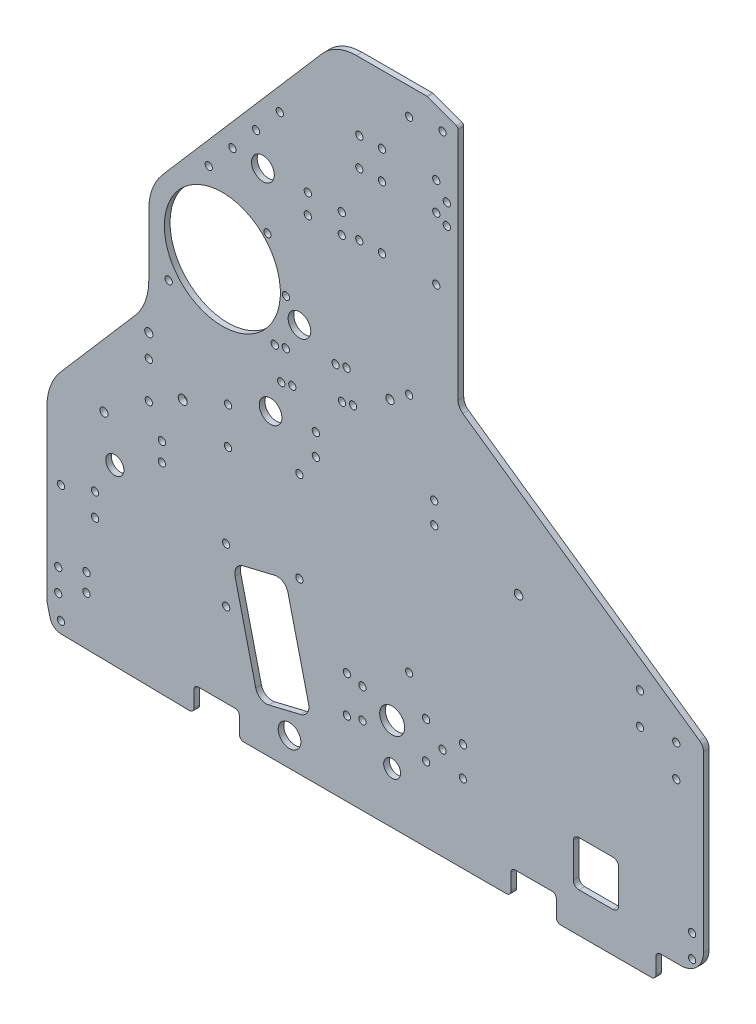
SolidWorks part; units mm, degrees
ref_plane "Front Plane" through (0, 0, 0) normal (0, 0, 1) x (1, 0, 0)
ref_plane "Top Plane" through (0, 0, 0) normal (0, 1, 0) x (1, 0, 0)
ref_plane "Right Plane" through (0, 0, 0) normal (1, 0, 0) x (0, 0, -1)
sketch "Sketch1" plane through (0, 0, 0) normal (0, 0, 1) x (1, 0, 0)
  line L0 (82.55, -20.32) -> (82.55, -6.35)
  line L2 (0, 0) -> (0, 157.48)
  line L4 (368.3, -20.32) -> (368.3, 106.68)
  line L5 (82.55, -6.35) -> (107.95, -6.35)
  line L6 (107.95, -6.35) -> (107.95, -20.32)
  line L7 (107.95, -20.32) -> (260.35, -20.32)
  line L8 (260.35, -20.32) -> (260.35, -6.35)
  line L9 (260.35, -6.35) -> (285.75, -6.35)
  line L10 (285.75, -6.35) -> (285.75, -20.32)
  line L11 (285.75, -20.32) -> (368.3, -20.32)
  line L12 (361.95, 12.7) -> (368.3, 12.7) construction
  line L13 (0, 0) -> (6.35, 0) construction
  line L14 (0.1896, -7.8901) -> (1.7771, -14.2401)
  line L15 (7.8295, -19.0491) -> (82.55, -20.32)
  line L16 (0, 0) -> (0, -6.35)
  line L17 (76.2, 128.905) -> (79.375, 128.905) construction
  line L18 (57.15, 118.5863) -> (101.6, 118.5862) construction
  line L19 (57.15, 118.5863) -> (57.15, 139.2238) construction
  line L20 (101.6, 118.5862) -> (101.6, 139.2237) construction
  line L21 (57.15, 139.2238) -> (101.6, 139.2237) construction
  line L22 (57.15, 118.5863) -> (101.6, 139.2237) construction
  line L23 (101.6, 118.5862) -> (57.15, 139.2238) construction
  line L24 (101.6, 139.2237) -> (125.4682, 147.9111) construction
  line L25 (203.2, 59.805) -> (203.2, 194.805) construction
  line L26 (203.2, 194.805) -> (203.2, 329.805) construction
  line L27 (355.6, 332.105) -> (330.2, 332.105) construction
  line L28 (330.2, 332.105) -> (330.2, 217.805) construction
  line L29 (330.2, 217.805) -> (355.6, 217.805) construction
  line L30 (355.6, 217.805) -> (355.6, 332.105) construction
  line L31 (203.2, 344.805) -> (203.2, 194.805) construction
  line L32 (50.8, 332.105) -> (76.2, 332.105) construction
  line L33 (76.2, 332.105) -> (76.2, 217.805) construction
  line L34 (50.8, 217.805) -> (50.8, 332.105) construction
  line L35 (76.2, 217.805) -> (50.8, 217.805) construction
  line L36 (213.2, 344.805) -> (230.6638, 338.455)
  line L37 (203.2, 344.805) -> (161.925, 344.805)
  line L38 (203.2, 344.805) -> (213.2, 344.805)
  line L39 (348.5362, 344.805) -> (413.4623, 344.805)
  line L40 (348.5362, 344.805) -> (230.6638, 344.805) construction
  line L42 (161.925, 344.805) -> (0, 157.48)
  line L44 (230.6638, 338.455) -> (230.6638, 202.565)
  line L45 (230.6638, 202.565) -> (368.3, 106.68)
  line L46 (213.2, 344.805) -> (-141.0713, 344.805) construction
  circle A0 centre (6.35, 0) radius 2.032
  circle A1 centre (6.35, 12.7) radius 2.032
  circle A2 centre (361.95, 0) radius 2.032
  circle A3 centre (361.95, 12.7) radius 2.032
  arc A5 (1.7771, -14.2401) -> (7.8295, -19.0491) centre (7.9375, -12.7) ccw
  circle A6 centre (7.9375, -12.7) radius 2.032
  arc A7 (0, -6.35) -> (0.1896, -7.8901) centre (6.35, -6.35) ccw
  circle A8 centre (38.1, 78.105) radius 5.08
  circle A9 centre (76.2, 128.905) radius 2.54
  circle A10 centre (101.6, 118.5862) radius 2.032
  circle A11 centre (101.6, 139.2237) radius 2.032
  circle A12 centre (57.15, 139.2238) radius 2.032
  circle A13 centre (57.15, 118.5863) radius 2.032
  circle A15 centre (203.2, 59.805) radius 2
  circle A16 centre (203.2, 194.805) radius 2
  circle A17 centre (203.2, 329.805) radius 2
  circle A18 centre (63.5, 313.055) radius 2.032
  circle A20 centre (355.6, 332.105) radius 2.032
  circle A21 centre (330.2, 332.105) radius 2.032
  circle A22 centre (355.6, 217.805) radius 2.032
  circle A23 centre (330.2, 217.805) radius 2.032
  circle A24 centre (50.8, 332.105) radius 2.032
  circle A25 centre (76.2, 332.105) radius 2.032
  circle A26 centre (50.8, 217.805) radius 2.032
  circle A27 centre (76.2, 217.805) radius 2.032
  circle A28 centre (221.9319, 332.105) radius 2
  circle A29 centre (224.3138, 298.831) radius 2.032
  circle A30 centre (353.06, 100.7351) radius 2.032
  circle A31 centre (332.74, 115.9751) radius 2.032
  circle A32 centre (332.74, 98.1951) radius 2.032
  circle A33 centre (353.06, 82.9551) radius 2.032
  circle A34 centre (117.3562, 280.4276) radius 2.032
  circle A35 centre (104.0678, 265.0548) radius 2.032
  circle A36 centre (90.7795, 249.682) radius 2.032
  circle A38 centre (130.6445, 295.8004) radius 2.032
  circle A39 centre (68.326, 182.9237) radius 2.032
  circle A40 centre (224.3138, 287.401) radius 2.032
  circle A41 centre (125.4682, 147.9111) radius 6.35
  point P82 (203.2, 344.805)
  point P83 (221.9319, 341.63)
  point P90 (368.3, 62.484)
  dimension "D6" = 4.064
  dimension "D10" = 6.35
  dimension "D11" = 4.064
  dimension "D17" = 38.1
  dimension "D27" = 4
  dimension "D31" = 4.064
  dimension "D32" = 41.275
  dimension "D36" = 4.064
  dimension "D47" = 39.624
  dimension "D48" = 4.064
  dimension "D25" = 5.08
  dimension "D26" = 4.064
  dimension "D52" = 4.064
  dimension "D65" = 4.064
  dimension "D69" = 10.16
  dimension "D72" = 12.7
  dimension "D2" = 127
  dimension "D3" = 13.97
  dimension "D4" = 25.4
  dimension "D5" = 152.4
  dimension "D7" = 12.7
  dimension "D8" = 6.35
  dimension "D9" = 20.32
  dimension "D12" = 12.7
  dimension "D13" = 1.5875
  dimension "D14" = 82.55
  dimension "D15" = 368.3
  dimension "D16" = 6.35
  dimension "D18" = 98.425
  dimension "D19" = 38.1
  dimension "D20" = 50.8
  dimension "D21" = 3.175
  dimension "D22" = 270
  dimension "D23" = 20.6375
  dimension "D24" = 44.45
  dimension "D28" = 135
  dimension "D29" = 12.7
  dimension "D30" = 15
  dimension "D33" = 63.5
  dimension "D34" = 27.4638
  dimension "D35" = 12.7
  dimension "D37" = 114.3
  dimension "D38" = 25.4
  dimension "D39" = 12.7
  dimension "D40" = 157.48
  dimension "D41" = 142.24
  dimension "D42" = 365.125
  dimension "D43" = 10
  dimension "D44" = 6.35
  dimension "D45" = 31.75
  dimension "D46" = 6.35
  dimension "D49" = 6.35
  dimension "D50" = 203.2
  dimension "D51" = 15.24
  dimension "D53" = 17.78
  dimension "D54" = 17.78
  dimension "D55" = 20.32
  dimension "D56" = 15.24
  dimension "D57" = 92.202
  dimension "D58" = 8.382
  dimension "D59" = 20.32
  dimension "D60" = 20.32
  dimension "D61" = 8.382
  dimension "D62" = 20.32
  dimension "D63" = 8.382
  dimension "D64" = 8.382
  dimension "D66" = 35.052
  dimension "D67" = 68.326
  dimension "D68" = 11.43
  dimension "D70" = 25.4
  dimension "D71" = 110
extrude "Boss-Extrude1" add sketch "Sketch1" along normal blind 3.175 contours L16 A7 L14 A5 L15 L2 A0 A1 A6 region at (171.5112, 119.5259, 0)
fillet "Fillet1" radius 2.286 4 edges at (285.75, -6.35, 1.5875) (107.95, -6.35, 1.5875) (260.35, -6.35, 1.5875) (82.55, -6.35, 1.5875)
fillet "Fillet2" radius 6.35 1 edges at (230.6638, 202.565, 1.5875)
sketch "Sketch2" plane through (0, 0, 0) normal (0, 0, -1) x (-1, 0, 0)
  circle A0 centre (-100.5528, 71.086) radius 2.032 construction
  circle A1 centre (-100.5528, 40.606) radius 2.032 construction
  circle A2 centre (-22.225, 18.2025) radius 2.032 construction
  circle A3 centre (-22.225, 8.0425) radius 2.032 construction
  circle A4 centre (-100.5528, 71.086) radius 2.032
  circle A5 centre (-100.5528, 40.606) radius 2.032
  circle A6 centre (-22.225, 18.2025) radius 2.032
  circle A7 centre (-22.225, 8.0425) radius 2.032
extrude "Cut-Extrude1" cut sketch "Sketch2" against normal through all
fillet "Fillet3" radius 1.5875 2 edges at (230.6638, 338.455, 1.5875) (213.2, 344.805, 1.5875)
sketch "Sketch3" plane through (0, 0, 3.175) normal (0, 0, 1) x (1, 0, 0)
  line L0 (132.9524, 63.2646) -> (132.7215, 64.2281) construction
  line L1 (128.3814, 66.8897) -> (110.6828, 62.6472) construction
  line L2 (114.5132, 58.4237) -> (126.8822, 61.3887) construction
  line L3 (108.0212, 58.3071) -> (108.2522, 57.3436) construction
  line L4 (131.2006, 57.703) -> (140.0164, 20.9265) construction
  line L5 (144.0993, 16.7636) -> (132.9524, 63.2646) construction
  line L6 (108.2522, 57.3436) -> (119.3991, 10.8426) construction
  line L7 (121.1509, 16.4042) -> (112.3351, 53.1807) construction
  line L8 (119.3991, 10.8426) -> (119.6301, 9.8791) construction
  line L9 (144.3303, 15.8001) -> (144.0993, 16.7636) construction
  line L10 (137.8383, 15.6835) -> (125.4694, 12.7185) construction
  line L11 (123.9701, 7.2175) -> (141.6687, 11.4601) construction
  line L12 (132.9524, 63.2646) -> (132.7215, 64.2281)
  line L13 (128.3814, 66.8897) -> (110.6828, 62.6472)
  line L14 (114.5132, 58.4237) -> (126.8822, 61.3887)
  line L15 (108.0212, 58.3071) -> (108.2522, 57.3436)
  line L16 (131.2006, 57.703) -> (140.0164, 20.9265)
  line L17 (144.0993, 16.7636) -> (132.9524, 63.2646)
  line L18 (108.2522, 57.3436) -> (119.3991, 10.8426)
  line L19 (121.1509, 16.4042) -> (112.3351, 53.1807)
  line L20 (119.3991, 10.8426) -> (119.6301, 9.8791)
  line L21 (144.3303, 15.8001) -> (144.0993, 16.7636)
  line L22 (137.8383, 15.6835) -> (125.4694, 12.7185)
  line L23 (123.9701, 7.2175) -> (141.6687, 11.4601)
  line L24 (127.7894, 69.3598) -> (110.0908, 65.1172)
  line L25 (105.5512, 57.715) -> (105.7822, 56.7515)
  line L26 (105.7822, 56.7515) -> (116.9291, 10.2505)
  line L27 (116.9291, 10.2505) -> (117.16, 9.287)
  line L28 (124.5622, 4.7475) -> (142.2608, 8.99)
  line L29 (146.8003, 16.3922) -> (146.5694, 17.3557)
  line L30 (146.5694, 17.3557) -> (135.4225, 63.8567)
  line L31 (135.4225, 63.8567) -> (135.1915, 64.8202)
  line L32 (14.605, -0.1369) -> (103.7278, 32.3011) construction
  line L33 (14.605, -0.1369) -> (103.7278, 32.3011)
  line L34 (0, -6.35) -> (0, 157.48) construction
  line L35 (-39.6666, 74.7152) -> (103.7278, 126.9065) construction
  line L36 (26.9875, 46.9531) -> (26.9875, 59.6531) construction
  line L37 (107.95, -20.32) -> (260.35, -20.32) construction
  line L38 (64.5259, 92.5258) -> (64.5259, 102.9405) construction
  line L39 (131.6538, 14.201) -> (136.0946, -4.3242) construction
  arc A0 (132.7215, 64.2281) -> (128.6308, 66.9403) centre (129.2206, 63.3889) ccw construction
  arc A1 (110.6828, 62.6472) -> (110.4377, 62.5791) centre (111.522, 59.1463) ccw construction
  arc A2 (128.6308, 66.9403) -> (128.3814, 66.8897) centre (129.2206, 63.3889) ccw construction
  arc A3 (110.4377, 62.5791) -> (108.0212, 58.3071) centre (111.522, 59.1463) ccw construction
  arc A4 (119.6301, 9.8791) -> (123.7207, 7.1669) centre (123.1309, 10.7183) ccw construction
  arc A5 (141.9139, 11.5281) -> (144.3303, 15.8001) centre (140.8295, 14.9609) ccw construction
  arc A6 (141.6687, 11.4601) -> (141.9139, 11.5281) centre (140.8295, 14.9609) ccw construction
  arc A7 (123.7207, 7.1669) -> (123.9701, 7.2175) centre (123.1309, 10.7183) ccw construction
  arc A8 (132.7215, 64.2281) -> (128.6308, 66.9403) centre (129.2206, 63.3889) ccw
  arc A9 (110.6828, 62.6472) -> (110.4377, 62.5791) centre (111.522, 59.1463) ccw
  arc A10 (128.6308, 66.9403) -> (128.3814, 66.8897) centre (129.2206, 63.3889) ccw
  arc A11 (110.4377, 62.5791) -> (108.0212, 58.3071) centre (111.522, 59.1463) ccw
  arc A12 (119.6301, 9.8791) -> (123.7207, 7.1669) centre (123.1309, 10.7183) ccw
  arc A13 (141.9139, 11.5281) -> (144.3303, 15.8001) centre (140.8295, 14.9609) ccw
  arc A14 (141.6687, 11.4601) -> (141.9139, 11.5281) centre (140.8295, 14.9609) ccw
  arc A15 (123.7207, 7.1669) -> (123.9701, 7.2175) centre (123.1309, 10.7183) ccw
  arc A16 (110.0908, 65.1172) -> (109.6726, 65.0012) centre (111.522, 59.1463) ccw
  arc A17 (109.6726, 65.0012) -> (105.5512, 57.715) centre (111.522, 59.1463) ccw
  arc A18 (117.16, 9.287) -> (124.1369, 4.6613) centre (123.1309, 10.7183) ccw
  arc A19 (124.1369, 4.6613) -> (124.5622, 4.7475) centre (123.1309, 10.7183) ccw
  arc A20 (142.2608, 8.99) -> (142.6789, 9.1061) centre (140.8295, 14.9609) ccw
  arc A21 (142.6789, 9.1061) -> (146.8003, 16.3922) centre (140.8295, 14.9609) ccw
  arc A22 (135.1915, 64.8202) -> (128.2147, 69.446) centre (129.2206, 63.3889) ccw
  arc A23 (128.2147, 69.446) -> (127.7894, 69.3598) centre (129.2206, 63.3889) ccw
  circle A24 centre (136.0946, -4.3242) radius 6.35
  circle A26 centre (134.1437, 208.2281) radius 2.032 construction
  circle A33 centre (26.9875, 46.9531) radius 2.032
  circle A34 centre (26.9875, 59.6531) radius 2.032
  circle A35 centre (7.9375, 53.3031) radius 2.032
  circle A37 centre (32.0306, 100.8109) radius 32.385 construction
  circle A38 centre (32.0306, 100.8109) radius 2.286
  circle A39 centre (123.682, 233.4851) radius 2.032 construction
  circle A40 centre (64.5259, 102.9405) radius 2.032
  circle A41 centre (64.5259, 92.5258) radius 2.032
  circle A42 centre (134.1437, 208.2281) radius 2.032
  circle A43 centre (123.682, 233.4851) radius 2.032
  ellipse E0 centre (124.5974, 48.8487) end of major axis (128.5376, 61.3578) minor radius 6 (131.2006, 57.703) -> (126.8822, 61.3887) ccw construction
  ellipse E1 centre (122.2349, 48.2824) end of major axis (113.0518, 57.6456) minor radius 6 (114.5132, 58.4237) -> (112.3351, 53.1807) ccw construction
  ellipse E2 centre (127.7541, 25.2585) end of major axis (131.6942, 37.7675) minor radius 6 (121.1509, 16.4042) -> (125.4694, 12.7185) ccw construction
  ellipse E3 centre (130.1166, 25.8248) end of major axis (139.2998, 16.4616) minor radius 6 (137.8383, 15.6835) -> (140.0164, 20.9265) ccw construction
  ellipse E4 centre (124.5974, 48.8487) end of major axis (120.6573, 36.3397) minor radius 6 (131.2006, 57.703) -> (126.8822, 61.3887) ccw
  ellipse E5 centre (122.2349, 48.2824) end of major axis (131.4181, 38.9192) minor radius 6 (114.5132, 58.4237) -> (112.3351, 53.1807) ccw
  ellipse E6 centre (127.7541, 25.2585) end of major axis (131.6942, 37.7675) minor radius 6 (121.1509, 16.4042) -> (125.4694, 12.7185) ccw
  ellipse E7 centre (130.1166, 25.8248) end of major axis (139.2998, 16.4616) minor radius 6 (137.8383, 15.6835) -> (140.0164, 20.9265) ccw
  point P93 (26.9875, 53.3031)
  point P115 (32.0306, 100.8109)
  dimension "D3" = 64.77
  dimension "D4" = 4.572
  dimension "D8" = 4.064
  dimension "D13" = 12.7
  dimension "D2" = 88.9
  dimension "D5" = 7.9375
  dimension "D6" = 19.05
  dimension "D7" = 73.6231
  dimension "D9" = 12.7
  dimension "D10" = 10.4147
  dimension "D11" = 37.5384
  dimension "D12" = 45.5727
  dimension "D14" = 19.05
  dimension "D1" = 2.54
extrude "Cut-Extrude2" cut sketch "Sketch3" against normal through all contours A22 A23 L24 A16 A17 L25 L26 L27 A18 A19 L28 A20 A21 L29 L30 L31 A15 A12 L20 L18 L15 A11 A9 L13 A10 A8 L12 L17 L21 A13 A14 L23 | A12 A15 L23 A14 A13 L21 L17 L12 A8 A10 L13 A9 A11 L15 L18 L20 E7 L22 E6 L19 E5 L14 E4 L16 | L22 E7 L16 E4 L14 E5 L19 E6 | A38 | A41 | A40 | A35 | A34 | A33 | A43 | A42 | A24 region at (137.844, 39.8506, 3.175) region at (126.1758, 37.0536, 3.175) region at (128.1544, 68.6507, 3.175) region at (32.0306, 100.8109, 3.175) region at (64.5259, 102.9405, 3.175) region at (64.5259, 92.5258, 3.175)
sketch "Sketch4" plane through (0, 0, 3.175) normal (0, 0, 1) x (1, 0, 0)
  line L0 (57.15, 139.2238) -> (101.6, 139.2237) construction
  line L1 (168.275, 21.4312) -> (212.725, 21.4312) construction
  line L2 (168.275, 21.4312) -> (168.275, 42.0687) construction
  line L3 (168.275, 42.0687) -> (212.725, 42.0687) construction
  line L4 (212.725, 21.4312) -> (212.725, 42.0687) construction
  line L5 (168.275, 21.4312) -> (212.725, 42.0687) construction
  line L6 (168.275, 42.0687) -> (212.725, 21.4312) construction
  line L7 (57.15, 118.5863) -> (57.15, 139.2238) construction
  line L8 (107.95, -20.32) -> (260.35, -20.32) construction
  line L9 (193.675, 31.75) -> (177.005, 31.75) construction
  line L10 (190.5, 31.75) -> (193.675, 31.75) construction
  line L11 (6.35, 12.7) -> (361.95, 12.7) construction
  line L12 (107.95, -6.35) -> (107.95, -20.32) construction
  line L13 (193.675, 31.75) -> (220.6625, 31.75) construction
  line L14 (177.005, 23.4569) -> (177.005, 40.0431) construction
  line L15 (213.2, 44.805) -> (193.2, 44.805) construction
  line L16 (213.2, 44.805) -> (213.2, 344.805) construction
  line L17 (213.2, 344.805) -> (193.2, 344.805) construction
  line L18 (193.2, 44.805) -> (193.2, 344.805) construction
  line L19 (213.2, 44.805) -> (193.2, 344.805) construction
  line L20 (213.2, 344.805) -> (193.2, 44.805) construction
  line L21 (226.9319, 332.105) -> (226.9319, 31.75) construction
  line L22 (237.33, 40.0431) -> (233.3612, 40.0431) construction
  line L23 (237.33, 23.4569) -> (233.3612, 23.4569) construction
  circle A0 centre (168.275, 42.0687) radius 2.032
  circle A1 centre (212.725, 42.0687) radius 2.032
  circle A2 centre (212.725, 21.4312) radius 2.032
  circle A3 centre (168.275, 21.4312) radius 2.032
  circle A4 centre (193.675, 31.75) radius 6.985
  circle A7 centre (220.6625, 31.75) radius 14.2875 construction
  circle A8 centre (193.675, 31.75) radius 12.7 construction
  circle A9 centre (177.005, 40.0431) radius 2.032
  circle A10 centre (177.005, 23.4569) radius 2.032
  circle A11 centre (237.33, 40.0431) radius 2.032 construction
  circle A12 centre (237.33, 23.4569) radius 2.032 construction
  circle A13 centre (193.675, 8.4667) radius 4.7625
  circle A14 centre (221.9319, 31.75) radius 2.032
  circle A15 centre (221.9319, 31.75) radius 5 construction
  circle A16 centre (221.9319, 332.105) radius 5 construction
  circle A17 centre (233.3612, 23.4569) radius 2.032
  circle A18 centre (233.3612, 40.0431) radius 2.032
  point P0 (190.5, 31.75)
  point P26 (203.2, 194.805)
  point P38 (177.005, 31.75)
  dimension "D1" = 4.064
  dimension "D4" = 13.97
  dimension "D7" = 9.525
  dimension "D10" = 25.4
  dimension "D11" = 28.575
  dimension "D16" = 10
  dimension "D17" = 4.064
  dimension "D18" = 10
  dimension "D2" = 52.07
  dimension "D3" = 3.175
  dimension "D5" = 82.55
  dimension "D6" = 26.9875
  dimension "D8" = 20
  dimension "D9" = 300
  dimension "D12" = 16.67
  dimension "D13" = 16.5862
  dimension "D14" = 60.325
  dimension "D15" = 23.2833
  dimension "D19" = 3.9688
extrude "Cut-Extrude3" cut sketch "Sketch4" against normal through all
sketch "Sketch5" plane through (0, 0, 0) normal (0, 0, -1) x (-1, 0, 0)
  line L0 (-57.15, 223.5947) -> (-57.15, 165.3337)
  line L1 (-161.925, 344.805) -> (-52.7201, 218.4699) construction
  line L2 (-57.15, 165.3337) -> (0, 99.219)
  line L3 (0, -6.35) -> (0, 157.48) construction
  line L4 (-147.864, -30.311) -> (-147.864, -16.0874)
  line L5 (-50.4199, 215.8089) -> (0, 157.48) construction
  line L6 (-57.15, 223.5947) -> (0, 157.48)
  line L7 (0, 157.48) -> (0, 99.219)
  line L8 (-98.425, 208.2281) -> (-141.6756, 197.9719) construction
  line L10 (-341.63, -6.35) -> (-341.63, -21.2964)
  line L12 (-371.0782, -6.35) -> (-341.63, -6.35)
  line L13 (-285.75, -20.32) -> (-368.3, -20.32) construction
  line L14 (-371.0782, -6.35) -> (-371.0782, -21.2964)
  line L15 (-371.0782, -21.2964) -> (-341.63, -21.2964)
  circle A0 centre (-98.425, 208.2281) radius 32.5437
  circle A1 centre (-141.6756, 197.9719) radius 6.35
  circle A3 centre (-264.5736, 128.3328) radius 2.39
  point P26 (-142.9428, 199.3423)
  dimension "D3" = 65.0875
  dimension "D7" = 12.7
  dimension "D8" = 4.78
  dimension "D1" = 38.1
  dimension "D2" = 57.15
  dimension "D4" = 41.275
  dimension "D5" = 41.275
  dimension "D6" = 13.97
  dimension "D9" = 22.2382
  dimension "D10" = 117.7733
  dimension "D11" = 11.6447
  dimension "D12" = 123.5853
  dimension "D14" = 62.5
  dimension "D13" = 44.45
extrude "Cut-Extrude5" cut sketch "Sketch5" against normal through all contours A0 | L7 L6 L0 L2 | A3 | L14 L15 L10 L12 | A1 region at (28.575, 161.4068, 0) region at (356.3541, -13.8232, 0) region at (98.425, 208.2281, 0) region at (264.5736, 128.3328, 0)
fillet "Fillet4" radius 31.75 3 edges at (0, 99.219, 1.5875) (57.15, 165.3337, 1.5875) (57.15, 223.5947, 1.5875)
sketch "Sketch6" plane through (0, 0, 3.175) normal (0, 0, 1) x (1, 0, 0)
  line L0 (285.75, -20.32) -> (341.63, -20.32) construction
  line L1 (298.45, 27.305) -> (317.5, 27.305)
  line L2 (295.275, 24.13) -> (295.275, 5.08)
  line L3 (298.45, 1.905) -> (317.5, 1.905)
  line L4 (320.675, 24.13) -> (320.675, 5.08)
  line L5 (295.275, 27.305) -> (320.675, 1.905) construction
  line L6 (295.275, 1.905) -> (320.675, 27.305) construction
  line L7 (368.3, -6.35) -> (368.3, 106.68) construction
  arc A0 (295.275, 5.08) -> (298.45, 1.905) centre (298.45, 5.08) ccw
  arc A1 (317.5, 1.905) -> (320.675, 5.08) centre (317.5, 5.08) ccw
  arc A2 (317.5, 27.305) -> (320.675, 24.13) centre (317.5, 24.13) cw
  arc A3 (298.45, 27.305) -> (295.275, 24.13) centre (298.45, 24.13) ccw
  point P0 (307.975, 14.605)
  dimension "D2" = 3.175
  dimension "D1" = 25.4
  dimension "D3" = 22.225
  dimension "D4" = 47.625
extrude "Cut-Extrude6" cut sketch "Sketch6" against normal through all
fillet "Fillet5" radius 25.4 1 edges at (161.925, 344.805, 1.5875)
sketch "Sketch8" plane through (0, 0, 0) normal (0, 0, -1) x (-1, 0, 0)
  line L0 (-230.6638, 337.343) -> (-230.6638, 205.8802) construction
  line L1 (-230.6638, 255.905) -> (-175.26, 255.905) construction
  line L2 (-175.26, 255.905) -> (-175.26, 306.705) construction
  line L3 (-175.26, 306.705) -> (-230.6638, 306.705) construction
  line L4 (-173.5432, 344.805) -> (-212.9203, 344.805) construction
  line L7 (-107.95, -20.32) -> (-260.35, -20.32) construction
  circle A0 centre (-218.44, 290.83) radius 3.9687
  circle A1 centre (-218.44, 290.83) radius 2.032
  circle A2 centre (218.44, 265.7972) radius 3.9687
  circle A3 centre (218.44, 265.7972) radius 2.032
  circle A4 centre (-205.74, 290.83) radius 3.9687
  circle A5 centre (-205.74, 290.83) radius 2.032
  circle A6 centre (-187.96, 290.83) radius 3.9687
  circle A7 centre (-187.96, 290.83) radius 2.032
  circle A8 centre (-187.96, 306.705) radius 2.032
  circle A9 centre (-175.26, 290.83) radius 3.9687
  circle A10 centre (-175.26, 290.83) radius 2.032
  circle A11 centre (-205.74, 306.705) radius 2.032
  circle A13 centre (-205.74, 255.905) radius 2.032
  circle A14 centre (-187.96, 255.905) radius 2.032
  circle A16 centre (-218.44, 306.705) radius 2.032
  circle A17 centre (-175.26, 306.705) radius 2.032
  circle A18 centre (-175.26, 255.905) radius 2.032
  circle A19 centre (-218.44, 255.905) radius 2.032
  circle A20 centre (-218.44, 306.705) radius 3.9687
  circle A21 centre (-205.74, 306.705) radius 3.9687
  circle A22 centre (-175.26, 306.705) radius 3.9687
  circle A23 centre (-218.44, 255.905) radius 3.9687
  circle A24 centre (-205.74, 255.905) radius 3.9687
  circle A25 centre (-187.96, 255.905) radius 3.9687
  circle A26 centre (-175.26, 255.905) radius 3.9687
  circle A27 centre (-187.96, 306.705) radius 3.9687
  dimension "D1" = 7.9375
  dimension "D7" = 4.064
  dimension "D13" = 12.2237
  dimension "D2" = 12.2237
  dimension "D3" = 12.7
  dimension "D4" = 17.78
  dimension "D5" = 12.7
  dimension "D6" = 88.9
  dimension "D8" = 38.1
  dimension "D9" = 17.78
  dimension "D10" = 12.7
  dimension "D11" = 55.4037
  dimension "D12" = 12.7
  dimension "D14" = 311.15
extrude "Cut-Extrude7" cut sketch "Sketch8" against normal through all contours A16 | A17 | A18 | A19 | A8 | A14 | A1 | A7 | A10 region at (218.44, 306.705, 0) region at (175.26, 306.705, 0) region at (175.26, 255.905, 0) region at (218.44, 255.905, 0)
sketch "Sketch10" plane through (0, 0, 3.175) normal (0, 0, 1) x (1, 0, 0)
  circle A4 centre (141.6425, 74.6844) radius 2.032 construction
  circle A5 centre (141.6425, 125.4844) radius 2.032 construction
  circle A6 centre (141.6425, 74.6844) radius 2.032
  circle A7 centre (141.6425, 125.4844) radius 2.032
extrude "Cut-Extrude8" cut sketch "Sketch10" against normal through all
sketch "Sketch11" plane through (0, 0, 3.175) normal (0, 0, 1) x (1, 0, 0)
  ellipse E4 centre (150.8814, 138.43) end of major axis (150.8814, 140.462) minor radius 2.032
  ellipse E5 centre (150.8814, 150.495) end of major axis (150.8814, 152.527) minor radius 2.032
  ellipse E6 centre (217.3024, 150.495) end of major axis (217.3024, 152.527) minor radius 2.032
  ellipse E7 centre (217.3024, 138.43) end of major axis (217.3024, 140.462) minor radius 2.032
extrude "Cut-Extrude9" cut sketch "Sketch11" against normal through all
sketch "Sketch12" plane through (0, 0, 0) normal (0, 0, -1) x (-1, 0, 0)
  line L0 (-173.5432, 344.805) -> (-212.9203, 344.805) construction
  circle A0 centre (-165.4175, 264.635) radius 2.032
  circle A1 centre (-203.2, 329.805) radius 2 construction
  circle A2 centre (-165.4175, 253.5225) radius 2.032
  circle A3 centre (-146.3675, 253.5225) radius 2.032
  circle A4 centre (-146.3675, 264.635) radius 2.032
  dimension "D1" = 80.17
  dimension "D2" = 4.064
  dimension "D3" = 37.7825
  dimension "D4" = 11.1125
  dimension "D5" = 19.05
extrude "Cut-Extrude10" cut sketch "Sketch12" against normal through all
sketch "Sketch14" plane through (0, 0, 0) normal (0, 0, -1) x (-1, 0, 0)
  line L0 (-130.6445, 295.8004) -> (-121.1847, 263.6885) construction
  line L1 (-121.1847, 263.6885) -> (-90.7795, 249.682) construction
  line L2 (-154.3272, 336.0154) -> (-64.88, 232.5373) construction
  line L4 (-118.517, 269.4796) -> (-115.3937, 261.0208) construction
  line L5 (-118.517, 269.4796) -> (-126.9758, 266.3562) construction
  line L6 (-126.9758, 266.3562) -> (-123.8524, 257.8974) construction
  line L7 (-115.3937, 261.0208) -> (-123.8524, 257.8974) construction
  line L8 (-118.517, 269.4796) -> (-123.8524, 257.8974) construction
  line L9 (-126.9758, 266.3562) -> (-115.3937, 261.0208) construction
  circle A0 centre (-121.1847, 263.6885) radius 6.376
  dimension "D1" = 22.225
  dimension "D2" = 9.017
extrude "Cut-Extrude11" cut sketch "Sketch14" against normal through all
sketch "Sketch15" plane through (0, 0, 3.175) normal (0, 0, 1) x (1, 0, 0)
  line L1 (27.1508, 77.7471) -> (81.7263, 77.7471) construction
  line L2 (57.15, 139.2238) -> (57.15, 151.9238) construction
  line L3 (27.1508, 77.7471) -> (52.3291, 153.5255) construction
  line L4 (56.0505, 156.8833) -> (192.439, 187.1199) construction
  circle A0 centre (27.1508, 77.7471) radius 2.159 construction
  circle A1 centre (27.1508, 77.7471) radius 2.159 construction
  circle A2 centre (57.15, 139.2238) radius 2.032 construction
  circle A3 centre (57.15, 139.2238) radius 2.032 construction
  circle A4 centre (57.15, 151.9238) radius 2.286
  circle A5 centre (192.439, 187.1199) radius 2.286
  circle A6 centre (57.15, 151.9238) radius 5.08 construction
  arc A9 (163.8737, 173.6806) -> (164.5125, 170.7993) centre (165.557, 172.5423) ccw construction
  arc A10 (173.4398, 172.7784) -> (172.801, 175.6597) centre (171.7565, 173.9167) ccw construction
  arc A11 (172.801, 175.6597) -> (173.4398, 172.7784) centre (171.7565, 173.9167) ccw construction
  arc A12 (164.5125, 170.7993) -> (163.8737, 173.6806) centre (165.557, 172.5423) ccw construction
  arc A13 (169.1589, 192.0883) -> (169.7976, 189.2071) centre (168.1143, 190.3453) ccw construction
  arc A14 (169.7976, 189.2071) -> (169.1589, 192.0883) centre (168.1143, 190.3453) ccw construction
  arc A15 (160.2316, 190.1092) -> (160.8704, 187.2279) centre (161.9149, 188.9709) ccw construction
  arc A16 (160.8704, 187.2279) -> (160.2316, 190.1092) centre (161.9149, 188.9709) ccw construction
  arc A17 (129.7766, 166.1214) -> (130.4154, 163.2402) centre (131.4599, 164.9832) ccw construction
  arc A18 (139.3426, 165.2193) -> (138.7039, 168.1005) centre (137.6593, 166.3576) ccw construction
  arc A19 (138.7039, 168.1005) -> (139.3426, 165.2193) centre (137.6593, 166.3576) ccw construction
  arc A20 (130.4154, 163.2402) -> (129.7766, 166.1214) centre (131.4599, 164.9832) ccw construction
  arc A21 (135.7005, 181.6479) -> (135.0617, 184.5292) centre (134.0172, 182.7862) ccw construction
  arc A22 (135.0617, 184.5292) -> (135.7005, 181.6479) centre (134.0172, 182.7862) ccw construction
  arc A23 (126.1345, 182.55) -> (126.7732, 179.6688) centre (127.8177, 181.4118) ccw construction
  arc A24 (126.7732, 179.6688) -> (126.1345, 182.55) centre (127.8177, 181.4118) ccw construction
  arc A25 (163.8737, 173.6806) -> (164.5125, 170.7993) centre (165.557, 172.5423) ccw
  arc A26 (173.4398, 172.7784) -> (172.801, 175.6597) centre (171.7565, 173.9167) ccw
  arc A27 (172.801, 175.6597) -> (173.4398, 172.7784) centre (171.7565, 173.9167) ccw
  arc A28 (164.5125, 170.7993) -> (163.8737, 173.6806) centre (165.557, 172.5423) ccw
  arc A29 (169.1589, 192.0883) -> (169.7976, 189.2071) centre (168.1143, 190.3453) ccw
  arc A30 (169.7976, 189.2071) -> (169.1589, 192.0883) centre (168.1143, 190.3453) ccw
  arc A31 (160.2316, 190.1092) -> (160.8704, 187.2279) centre (161.9149, 188.9709) ccw
  arc A32 (160.8704, 187.2279) -> (160.2316, 190.1092) centre (161.9149, 188.9709) ccw
  arc A33 (129.7766, 166.1214) -> (130.4154, 163.2402) centre (131.4599, 164.9832) ccw
  arc A34 (139.3426, 165.2193) -> (138.7039, 168.1005) centre (137.6593, 166.3576) ccw
  arc A35 (138.7039, 168.1005) -> (139.3426, 165.2193) centre (137.6593, 166.3576) ccw
  arc A36 (130.4154, 163.2402) -> (129.7766, 166.1214) centre (131.4599, 164.9832) ccw
  arc A37 (135.7005, 181.6479) -> (135.0617, 184.5292) centre (134.0172, 182.7862) ccw
  arc A38 (135.0617, 184.5292) -> (135.7005, 181.6479) centre (134.0172, 182.7862) ccw
  arc A39 (126.1345, 182.55) -> (126.7732, 179.6688) centre (127.8177, 181.4118) ccw
  arc A40 (126.7732, 179.6688) -> (126.1345, 182.55) centre (127.8177, 181.4118) ccw
  dimension "D2" = 4.572
  dimension "D6" = 10.16
  dimension "D1" = 12.7
  dimension "D3" = 139.7
  dimension "D4" = 12.5
extrude "Cut-Extrude12" cut sketch "Sketch15" against normal through all
sketch "Sketch16" plane through (0, 0, 3.175) normal (0, 0, 1) x (1, 0, 0)
  circle A0 centre (98.425, 208.2281) radius 34.925 construction
  circle A1 centre (98.425, 208.2281) radius 34.925
  circle A2 centre (98.425, 208.2281) radius 36.195
  dimension "D1" = 1.27
fillet "Fillet6" radius 12.7 1 edges at (368.3, -6.35, 1.5875)
fillet "Fillet7" radius 5.08 1 edges at (368.3, 106.68, 1.5875)
fillet "Fillet8" radius 2.54 6 edges at (82.55, -20.32, 1.5875) (107.95, -20.32, 1.5875) (260.35, -20.32, 1.5875) (285.75, -20.32, 1.5875) (341.63, -20.32, 1.5875) (341.63, -6.35, 1.5875)
